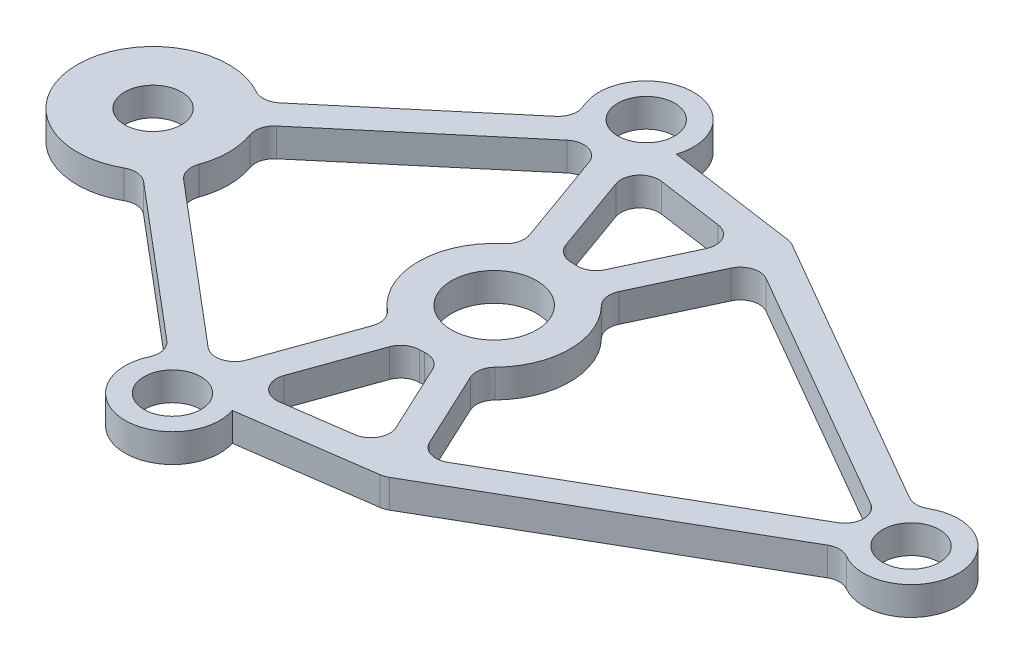
SolidWorks part; units mm, degrees
material "1060 Alloy"
ref_plane "Front" through (0, 0, 0) normal (0, 0, 1) x (1, 0, 0)
ref_plane "Top" through (0, 0, 0) normal (0, 1, 0) x (1, 0, 0)
ref_plane "Right" through (0, 0, 0) normal (1, 0, 0) x (0, 0, -1)
sketch "草图1" plane through (0, 0, 0) normal (0, 1, 0) x (1, 0, 0)
  line L0 (0, 0) -> (-18, 0) construction
  line L1 (0, 0) -> (22, 0) construction
  line L2 (22, 0) -> (4.6795, 10) construction
  line L4 (22, 0) -> (-4.4758, 12.5) construction
  line L6 (0.1065, -1.9972) -> (0.0924, -1.9669)
  line L7 (0.0811, -1.9984) -> (0.0924, -1.9669)
  line L8 (19.75, 2.1651) -> (5.0965, 10.6253)
  line L9 (4.7364, 10.7494) -> (-2.1019, 11.7159)
  line L10 (2.2314, 9.5886) -> (-1.2565, 10.0815)
  line L11 (4.9285, 10.7223) -> (-3.2584, 11.8794) construction
  line L12 (-7.0068, 10.2659) -> (-14.9056, 3.5951)
  line L13 (19, 0.866) -> (5.9562, 8.3969)
  line L14 (4.5504, -7.9547) -> (2.6645, -3.9244)
  line L15 (-2.3379, -8.7543) -> (-0.8728, -4.6624)
  line L16 (2.9972, 8.1746) -> (1.3059, 4.5601)
  line L17 (-5.6221, 9.4721) -> (-13.9377, 2.4491)
  line L18 (-3.2584, 11.8794) -> (-4.5001, 14.0565) construction
  line L19 (-4.0354, -9.0452) -> (-2.285, -4.1568)
  line L20 (-4.5001, 14.0565) -> (-6.1038, 11.0285) construction
  line L21 (-4.9142, 10.0699) -> (-17.5161, -0.573) construction
  line L22 (-6.1038, 11.0285) -> (-18.4839, 0.573) construction
  line L23 (21.625, -0.6495) -> (4.4305, 9.2777) construction
  line L24 (22.375, 0.6495) -> (4.9285, 10.7223) construction
  line L25 (-5.6221, -9.4721) -> (-13.9377, -2.4491)
  line L27 (-4.4515, 10.9435) -> (-4.9142, 10.0699) construction
  line L28 (2.9972, -8.1746) -> (1.3059, -4.5601)
  line L29 (4.4305, 9.2777) -> (-4.1969, 10.4971) construction
  line L30 (19, -0.866) -> (5.9562, -8.3969)
  line L31 (-4.0354, 9.0452) -> (-2.285, 4.1568)
  line L32 (-7.0068, -10.2659) -> (-14.9056, -3.5951)
  line L33 (-2.3379, 8.7543) -> (-0.8728, 4.6624)
  line L34 (2.2314, -9.5886) -> (-1.2565, -10.0815)
  line L35 (4.5504, 7.9547) -> (2.6645, 3.9244)
  line L38 (4.7364, -10.7494) -> (-2.1019, -11.7159)
  line L39 (19.75, -2.1651) -> (5.0965, -10.6253)
  line L41 (-4.1969, 10.4971) -> (-4.4515, 10.9435) construction
  line L42 (-3.7277, 11.1883) -> (-4.4758, 12.5) construction
  line L43 (-4.4758, 12.5) -> (-5.509, 10.5492) construction
  line L44 (4.6795, 10) -> (-3.7277, 11.1883) construction
  line L45 (-5.509, 10.5492) -> (-18, 0) construction
  circle A0 centre (0, 0) radius 2.25
  arc A1 (0.3201, 3.9872) -> (0.0549, 3.9996) centre (0, 0) ccw
  circle A2 centre (-18, 0) radius 1.5
  arc A3 (-16.0406, 3.4872) -> (-16.0406, -3.4872) centre (-18, 0) ccw
  circle A4 centre (22, 0) radius 1.5
  arc A5 (20.75, -2.1651) -> (20.75, 2.1651) centre (22, 0) ccw
  arc A7 (-2.5812, 3.0557) -> (-2.5812, -3.0557) centre (0, 0) ccw
  arc A8 (-2.1019, 11.7159) -> (-6.7446, 11.4499) centre (-4.4758, 12.5) ccw
  circle A9 centre (-4.4758, 12.5) radius 1.5
  arc A10 (19.75, 2.1651) -> (20.75, 2.1651) centre (20.25, 3.0311) ccw
  arc A11 (19, 0.866) -> (19, -0.866) centre (18.5, 0) cw
  arc A12 (-13.9377, 2.4491) -> (-14.234, 1.3481) centre (-13.2925, 1.6851) ccw
  arc A13 (-14.9056, 3.5951) -> (-16.0406, 3.4872) centre (-15.5508, 4.3591) cw
  arc A14 (-7.0068, 10.2659) -> (-6.7446, 11.4499) centre (-7.6521, 11.0299) ccw
  arc A15 (-2.285, 4.1568) -> (-2.5812, 3.0557) centre (-3.2265, 3.8197) cw
  arc A16 (2.8562, 2.8004) -> (2.6645, 3.9244) centre (3.5702, 3.5005) cw
  arc A17 (0.3201, 3.9872) -> (1.3059, 4.5601) centre (0.4001, 4.984) ccw
  arc A18 (-0.8728, 4.6624) -> (0.0549, 3.9996) centre (0.0687, 4.9995) ccw
  arc A19 (4.5504, 7.9547) -> (5.9562, 8.3969) centre (5.4562, 7.5309) cw
  arc A20 (5.0965, 10.6253) -> (4.7364, 10.7494) centre (4.5965, 9.7592) ccw
  arc A21 (2.2314, 9.5886) -> (2.9972, 8.1746) centre (2.0915, 8.5984) cw
  arc A22 (-1.2565, 10.0815) -> (-2.3379, 8.7543) centre (-1.3965, 9.0914) ccw
  arc A23 (-4.0354, 9.0452) -> (-5.6221, 9.4721) centre (-4.9768, 8.7081) ccw
  arc A24 (2.8562, -2.8004) -> (2.8562, 2.8004) centre (0, 0) ccw
  arc A25 (-14.234, -1.3481) -> (-14.234, 1.3481) centre (-18, 0) ccw
  arc A26 (-4.0354, -9.0452) -> (-5.6221, -9.4721) centre (-4.9768, -8.7081) cw
  arc A27 (-1.2565, -10.0815) -> (-2.3379, -8.7543) centre (-1.3965, -9.0914) cw
  arc A28 (2.2314, -9.5886) -> (2.9972, -8.1746) centre (2.0915, -8.5984) ccw
  arc A29 (5.0965, -10.6253) -> (4.7364, -10.7494) centre (4.5965, -9.7592) cw
  arc A30 (4.5504, -7.9547) -> (5.9562, -8.3969) centre (5.4562, -7.5309) ccw
  arc A31 (-0.8728, -4.6624) -> (0.0549, -3.9996) centre (0.0687, -4.9995) cw
  arc A32 (0.3201, -3.9872) -> (1.3059, -4.5601) centre (0.4001, -4.984) cw
  arc A33 (2.8562, -2.8004) -> (2.6645, -3.9244) centre (3.5702, -3.5005) ccw
  arc A34 (-2.285, -4.1568) -> (-2.5812, -3.0557) centre (-3.2265, -3.8197) ccw
  arc A35 (-7.0068, -10.2659) -> (-6.7446, -11.4499) centre (-7.6521, -11.0299) cw
  arc A36 (-14.9056, -3.5951) -> (-16.0406, -3.4872) centre (-15.5508, -4.3591) ccw
  arc A37 (-13.9377, -2.4491) -> (-14.234, -1.3481) centre (-13.2925, -1.6851) cw
  arc A38 (19.75, -2.1651) -> (20.75, -2.1651) centre (20.25, -3.0311) cw
  circle A39 centre (-4.4758, -12.5) radius 1.5
  arc A40 (-2.1019, -11.7159) -> (-6.7446, -11.4499) centre (-4.4758, -12.5) cw
  arc A41 (0.3201, -3.9872) -> (0.0549, -3.9996) centre (0, 0) cw
  point P53 (-2.0306, 3.4463)
  point P79 (-2.0306, -3.4463)
  dimension "D1" = 30
  dimension "D2" = 0.75
  dimension "D4" = 1
  dimension "D6" = 4.5
  dimension "D5" = 25.273
  dimension "D3" = 0.75
extrude "凸台-拉伸1" add sketch "草图1" along normal blind 1.5 contours A40 L38 A29 L39 A38 A5 A10 L8 A20 L9 A8 A14 L12 A13 A3 A36 L32 A35 A41 A32 L28 A28 L34 A27 L15 A31 L25 A37 A25 A12 L17 A23 L31 A15 A7 A34 L19 A26 A0 A2 A4 A9 A22 region at (20.25, 0, -1.4777)
